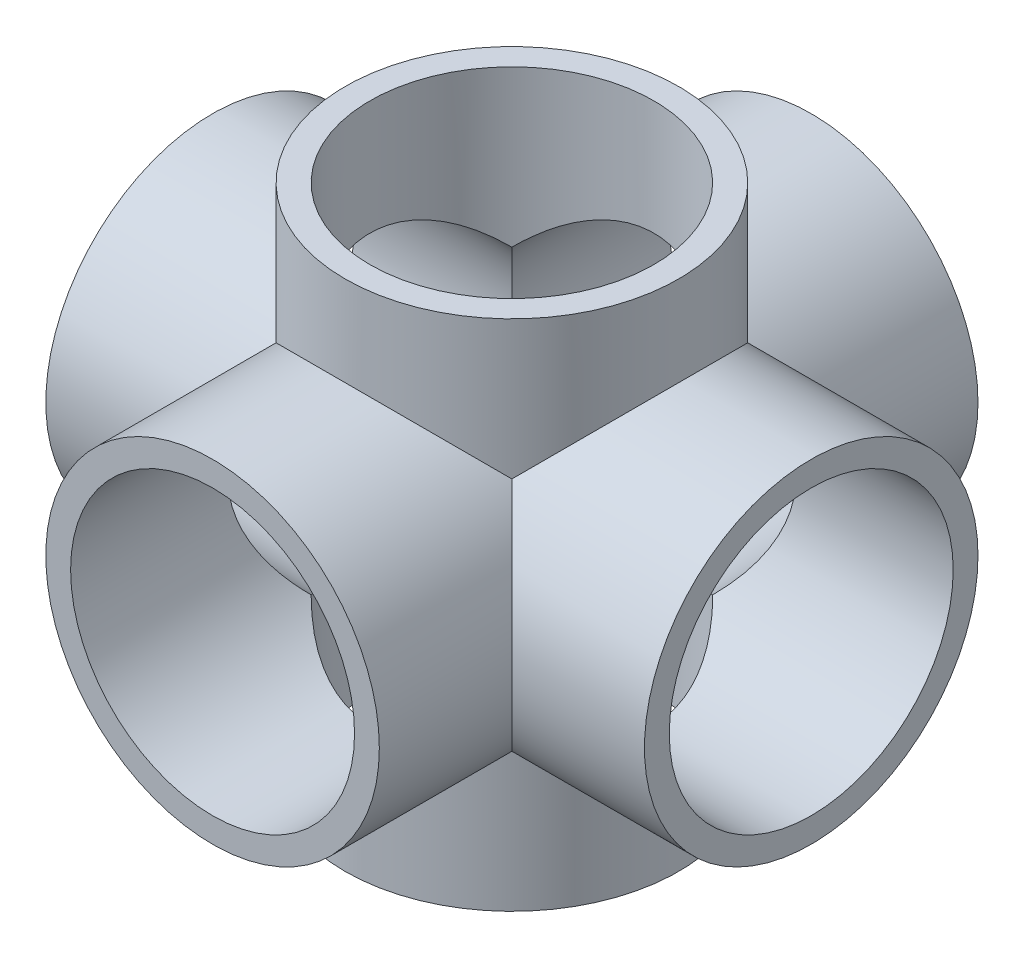
SolidWorks part; units mm, degrees
ref_plane "Alzado" through (0, 0, 0) normal (0, 0, 1) x (1, 0, 0)
ref_plane "Planta" through (0, 0, 0) normal (0, 1, 0) x (1, 0, 0)
ref_plane "Vista lateral" through (0, 0, 0) normal (1, 0, 0) x (0, 0, -1)
sketch "Croquis1" plane through (0, 0, 0) normal (0, 1, 0) x (1, 0, 0)
  circle A0 centre (0, 0) radius 16.6
  circle A1 centre (0, 0) radius 19.5
extrude "Saliente-Extruir1" add sketch "Croquis1" along normal blind 60
sketch "Croquis2" plane through (0, 0, 0) normal (1, 0, 0) x (0, 0, -1)
  line L0 (0, 60) -> (0, 30)
  line L1 (16.6, 60) -> (-16.6, 60) construction
  line L2 (0, 33) -> (0, -33) construction
  circle A0 centre (0, 30) radius 16.6
  circle A1 centre (0, 30) radius 19.5
extrude "Saliente-Extruir3" add sketch "Croquis2" along normal blind 35 and the other way blind 35 contours A1 | A0
sketch "Croquis3" plane through (0, 0, 0) normal (0, 0, 1) x (1, 0, 0)
  line L0 (0, 60) -> (0, 30)
  line L1 (19.5, 60) -> (-19.5, 60) construction
  line L2 (0, -21.45) -> (0, 21.45) construction
  circle A0 centre (0, 30) radius 16.6
  circle A1 centre (0, 30) radius 19.5
extrude "Saliente-Extruir4" add sketch "Croquis3" along normal blind 35 and the other way blind 35 contours A0 | A1
sketch "Croquis5" plane through (0, 0, 0) normal (1, 0, 0) x (0, 0, -1)
  line L0 (0, 60) -> (0, 30)
  line L1 (19.5, 60) -> (-19.5, 60) construction
  line L2 (0, 33) -> (0, -33) construction
  line L3 (-11.738, 41.738) -> (0, 30) construction
  circle A0 centre (0, 30) radius 16.6
extrude "Cortar-Extruir1" cut sketch "Croquis5" against normal blind 35 and the other way blind 35 contours A0 | A0 region at (0, 18.594, 11.406)
sketch "Croquis6" plane through (0, 0, 0) normal (0, 0, 1) x (1, 0, 0)
  line L0 (0, 60) -> (0, 30)
  line L1 (19.5, 60) -> (-19.5, 60) construction
  circle A0 centre (0, 30) radius 16.6
extrude "Cortar-Extruir2" cut sketch "Croquis6" against normal blind 35 and the other way blind 35 contours A0 | A0 region at (-11.406, 18.594, 0)
sketch "Croquis7" plane through (0, 0, 0) normal (0, 1, 0) x (1, 0, 0)
  line L0 (0, 35) -> (0, 0)
  line L1 (16.6, 35) -> (-16.6, 35) construction
  circle A0 centre (0, 0) radius 16.6
extrude "Cortar-Extruir3" cut sketch "Croquis7" along normal blind 60 contours A0
